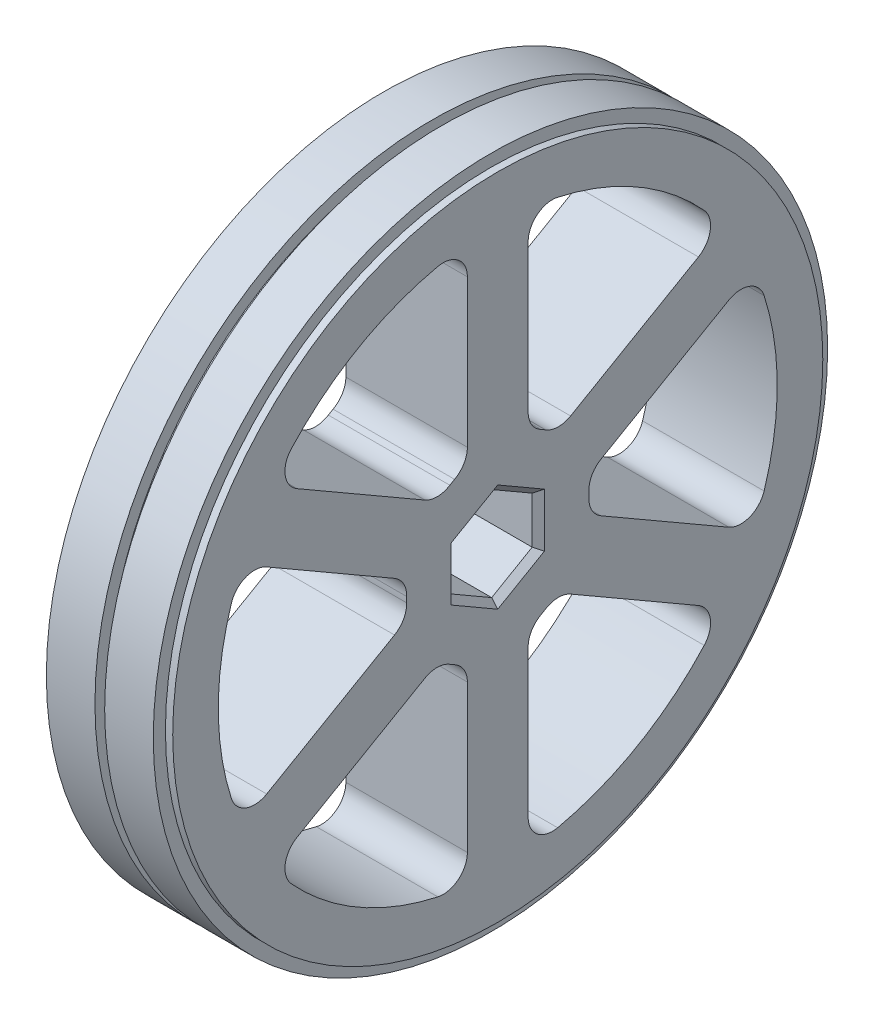
SolidWorks part; units mm, degrees
ref_plane "Front Plane" through (0, 0, 0) normal (0, 0, 1) x (1, 0, 0)
ref_plane "Top Plane" through (0, 0, 0) normal (0, 1, 0) x (1, 0, 0)
ref_plane "Right Plane" through (0, 0, 0) normal (1, 0, 0) x (0, 0, -1)
sketch "Axle Profile" plane through (0, 0, 0) normal (1, 0, 0) x (0, 0, -1)
  line L1 (0, -4.8895) -> (4.2344, -2.4448)
  line L2 (4.2344, -2.4448) -> (4.2344, 2.4447)
  line L3 (4.2344, 2.4447) -> (0, 4.8895)
  line L4 (0, 4.8895) -> (-4.2344, 2.4448)
  line L5 (-4.2344, 2.4448) -> (-4.2344, -2.4448)
  line L6 (-4.2344, -2.4448) -> (0, -4.8895)
  circle A0 centre (0, 0) radius 4.8895 construction
  circle A1 centre (0, 0) radius 9.525
  dimension "D1" = 9.779
  dimension ".625" = 19.05
extrude "Wheel Hub" add sketch "Axle Profile" along normal blind 12.7
fillet "Hub Fillet" [suppressed] radius 2.032
ref_plane "Spoke Plane" through (0, 0, -4.2344) normal (0, 0, 1) x (1, 0, 0)
sketch "Sketch2" plane through (0, 0, -4.2344) normal (0, 0, 1) x (1, 0, 0)
  line L0 (12.7, 2.4448) -> (0, -2.4447) construction
  line L1 (0, 2.4448) -> (12.7, -2.4447) construction
  circle A0 centre (6.35, 0) radius 2.54
  dimension "D1" = 5.08
extrude "Spoke" [suppressed] add sketch "Sketch2" against normal blind 25.4
ref_axis "Pattern Axis" through (12.7, 0, 0) along (-1, 0, 0)
pattern_circular "CirPattern1" [suppressed] count 6 over 360 about axis through (12.7, 0, 0) along (-1, 0, 0) of bodies 102
fillet "Hub/Spoke Fillet" [suppressed] radius 2.54
ref_plane "Mid Plane" through (6.35, 0, 0) normal (-1, 0, 0) x (0, 0, 1)
sketch "Sketch3" plane through (6.35, 0, 0) normal (-1, 0, 0) x (0, 0, 1)
  circle A0 centre (0, 0) radius 29.21
  circle A1 centre (0, 0) radius 33.9725
  dimension "D1" = 58.42
  dimension "D2" = 67.945
extrude "Wheel Rim" add sketch "Sketch3" along normal up to surface and the other way up to surface up to face at (0, 0, -9.525) other way up to face at (12.7, 0, -9.525)
fillet "Rim/Spoke Fillet" [suppressed] radius 2.54
fillet "Rim Fillet" [suppressed] radius 0.762
sketch "Sketch4" plane through (12.7, 0, 0) normal (1, 0, 0) x (0, 0, -1)
  line L0 (0, 8.9803) -> (0, 0) construction
  line L1 (-3.175, 8.9803) -> (3.175, 8.9803)
  line L2 (-3.175, 8.9803) -> (-3.175, 29.21)
  line L3 (-3.175, 29.21) -> (3.175, 29.21)
  line L4 (3.175, 8.9803) -> (3.175, 29.21)
  circle A0 centre (0, 0) radius 9.525 construction
  circle A1 centre (0, 0) radius 29.21 construction
  dimension "D1" = 6.35
extrude "Boss-Extrude1" add sketch "Sketch4" against normal up to surface (12.7 mm away) up to face at (0, 0, -29.21)
pattern_circular "Spokes" count 6 over 360 about axis through (0, 0, 0) along (1, 0, 0) of "Boss-Extrude1"
fillet "Spoke Fillets" radius 2.54 24 edges at (6.35, 8.9803, 3.175) (6.35, 7.2398, 6.1896) (6.35, -1.7405, 9.3646) (6.35, 1.7405, 9.3646) (6.35, -8.9803, 3.175) (6.35, -7.2398, 6.1896) (6.35, -8.9803, -3.175) (6.35, -7.2398, -6.1896) (6.35, -1.7405, -9.3646) (6.35, 1.7405, -9.3646) (6.35, 7.2398, -6.1896) (6.35, 8.9803, -3.175) (6.35, 29.0369, -3.175) (6.35, 29.0369, 3.175) (6.35, 17.2681, 23.5592) (6.35, 11.7688, 26.7342) (6.35, -11.7688, 26.7342) (6.35, -17.2681, 23.5592) (6.35, -29.0369, 3.175) (6.35, -17.2681, -23.5592) (6.35, -11.7688, -26.7342) (6.35, 11.7688, -26.7342) (6.35, 17.2681, -23.5592) (6.35, -29.0369, -3.175)
chamfer "Shaft Chamfers" distance 0.635 angle 45 12 edges at (0, 0, 4.2344) (0, 3.6671, 2.1172) (0, 3.6671, -2.1172) (0, 0, -4.2344) (0, -3.6671, -2.1172) (0, -3.6671, 2.1172) (12.7, -3.6671, -2.1172) (12.7, -3.6671, 2.1172) (12.7, 0, 4.2344) (12.7, 3.6671, 2.1172) (12.7, 3.6671, -2.1172) (12.7, 0, -4.2344)
ref_plane "Plane1" through (6.35, 0, 0) normal (-1, 0, 0) x (0, 0, 1)
sketch "Sketch6" plane through (6.35, 0, 0) normal (-1, 0, 0) x (0, 0, 1)
  circle A0 centre (0, 0) radius 33.9725
extrude "Extrude-Thin1" add sketch "Sketch6" along normal blind 5.08 from offset 0.508 separate body thin thin type one direction wall 1.27
mirror "Mirror1" about plane through (6.35, 0, 0) normal (-1, 0, 0) of bodies 107
